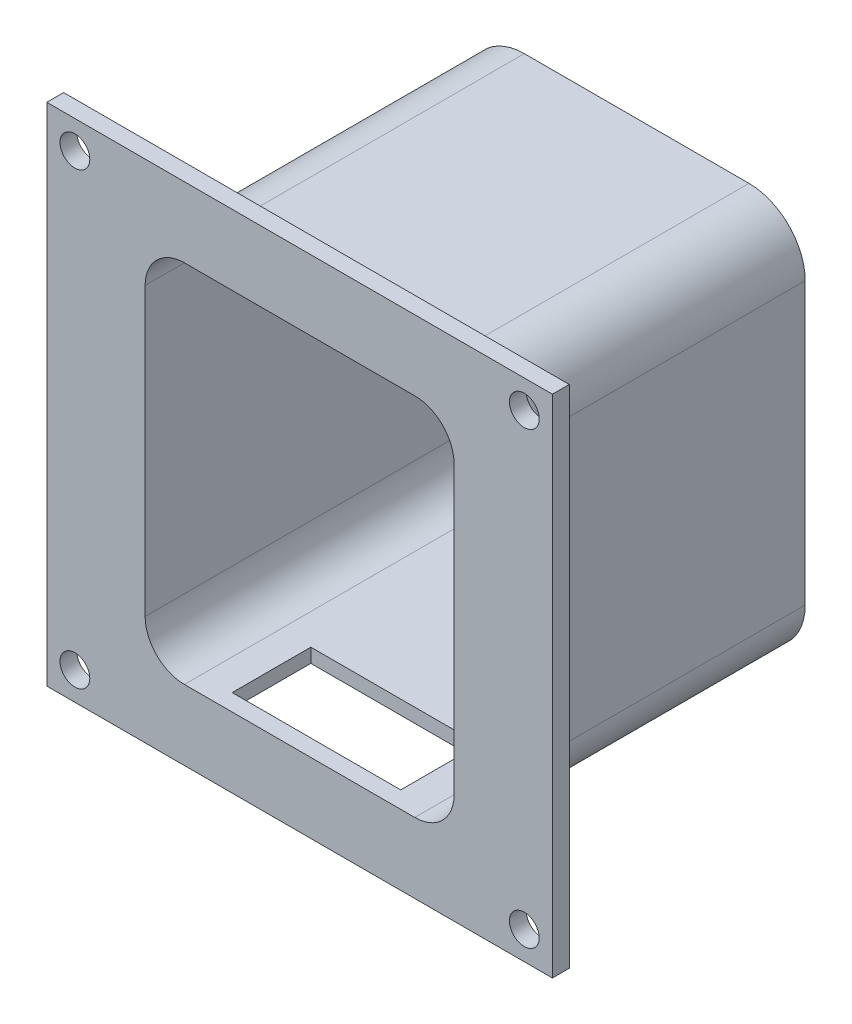
SolidWorks part; units mm, degrees
ref_plane "Front Plane" through (0, 0, 0) normal (0, 0, 1) x (1, 0, 0)
ref_plane "Top Plane" through (0, 0, 0) normal (0, 1, 0) x (1, 0, 0)
ref_plane "Right Plane" through (0, 0, 0) normal (1, 0, 0) x (0, 0, -1)
sketch "Sketch1" plane through (0, 0, 0) normal (0, 0, 1) x (1, 0, 0)
  line L1 (-30, -35) -> (30, -35)
  line L2 (-30, -35) -> (-30, 35)
  line L3 (-30, 35) -> (30, 35)
  line L4 (30, -35) -> (30, 35)
  line L5 (-30, -35) -> (30, 35) construction
  line L6 (-30, 35) -> (30, -35) construction
  line L7 (20.5, -32.5) -> (-20.5, -32.5)
  line L8 (27.5, -25.5) -> (27.5, 25.5)
  line L9 (20.5, 32.5) -> (-20.5, 32.5)
  line L10 (-27.5, -25.5) -> (-27.5, 25.5)
  line L11 (27.5, -32.5) -> (-27.5, 32.5) construction
  line L12 (27.5, 32.5) -> (-27.5, -32.5) construction
  arc A0 (-20.5, -32.5) -> (-27.5, -25.5) centre (-20.5, -25.5) cw
  arc A1 (20.5, -32.5) -> (27.5, -25.5) centre (20.5, -25.5) ccw
  arc A2 (27.5, 25.5) -> (20.5, 32.5) centre (20.5, 25.5) ccw
  arc A3 (-20.5, 32.5) -> (-27.5, 25.5) centre (-20.5, 25.5) ccw
  point P0 (0, 0)
  point P6 (0, 0)
  dimension "D3" = 7
  dimension "D1" = 70
  dimension "D2" = 60
  dimension "D4" = 65
  dimension "D5" = 55
extrude "Boss-Extrude1" add sketch "Sketch1" along normal blind 60
sketch "Sketch2" plane through (0, 0, 0) normal (0, 0, -1) x (-1, 0, 0)
  line L0 (0, 0.5) -> (0, -32.5) construction
  line L1 (-17.65, -4.5) -> (-10.65, -4.5)
  line L2 (-10.65, -4.5) -> (-10.65, -29.5)
  line L3 (-10.65, -29.5) -> (10.65, -29.5)
  line L4 (10.65, -29.5) -> (10.65, -4.5)
  line L5 (10.65, -4.5) -> (17.65, -4.5)
  line L6 (17.65, -4.5) -> (17.65, -25.5)
  line L7 (-17.65, -4.5) -> (-17.65, -25.5)
  line L8 (0, 0.5) -> (13.5, 0.5) construction
  line L9 (13.5, 0.5) -> (13.5, -8.5) construction
  line L10 (13.5, -8.5) -> (13.5, -16.5) construction
  line L11 (13.5, -16.5) -> (13.5, -24.5) construction
  line L12 (-20.5, -32.5) -> (20.5, -32.5)
  line L13 (-17.65, -25.5) -> (-27.5, -25.5)
  line L14 (17.65, -25.5) -> (27.5, -25.5)
  line L15 (20.5, -32.5) -> (-20.5, -32.5) construction
  circle A0 centre (0, 0.5) radius 11 construction
  circle A1 centre (13.5, -8.5) radius 1.25
  arc A2 (-27.5, -25.5) -> (-20.5, -32.5) centre (-20.5, -25.5) ccw
  circle A3 centre (13.5, -16.5) radius 1.25
  circle A4 centre (13.5, -24.5) radius 1.25
  circle A5 centre (-13.5, -8.5) radius 1.25
  circle A6 centre (-13.5, -16.5) radius 1.25
  circle A7 centre (-13.5, -24.5) radius 1.25
  arc A8 (20.5, -32.5) -> (27.5, -25.5) centre (20.5, -25.5) ccw
  arc A9 (-27.5, -25.5) -> (-20.5, -32.5) centre (-20.5, -25.5) ccw construction
  point P6 (0, -29.5)
  point P31 (0, 0)
  point P34 (0, -32.5)
  dimension "D1" = 22
  dimension "D5" = 2.5
  dimension "D2" = 21.3
  dimension "D3" = 13.5
  dimension "D4" = 9
  dimension "D6" = 8
  dimension "D7" = 8
  dimension "D8" = 7
  dimension "D9" = 5
  dimension "D10" = 3
  dimension "D11" = 30
extrude "Boss-Extrude2" add sketch "Sketch2" against normal blind 3.5
sketch "Sketch4" plane through (0, -35, 0) normal (0, -1, 0) x (1, 0, 0)
  line L0 (-30, 60) -> (30, 60) construction
  line L1 (15, 60) -> (-15, 60)
  line L2 (15, 60) -> (15, 43)
  line L3 (15, 43) -> (-15, 43)
  line L4 (-15, 60) -> (-15, 43)
  line L5 (0, 0) -> (0, 60) construction
  line L6 (-30, 0) -> (30, 0) construction
  point P10 (0, 60)
  dimension "D1" = 30
  dimension "D2" = 17
extrude "Cut-Extrude1" cut sketch "Sketch4" against normal up to surface (2.5 mm away) up to face at (0, -32.5, 31.75)
sketch "Sketch5" plane through (0, 0, 0) normal (0, 0, -1) x (-1, 0, 0)
  circle A0 centre (-13.5, -8.5) radius 2.25
  circle A1 centre (-13.5, -16.5) radius 2.25
  circle A2 centre (-13.5, -24.5) radius 2.25
  circle A3 centre (13.5, -24.5) radius 2.25
  circle A4 centre (13.5, -16.5) radius 2.25
  circle A5 centre (13.5, -8.5) radius 2.25
  dimension "D1" = 4.5
extrude "Cut-Extrude2" cut sketch "Sketch5" against normal blind 3
sketch "Sketch6" plane through (0, 0, 60) normal (0, 0, 1) x (1, 0, 0)
  line L1 (-45, 45) -> (45, 45)
  line L2 (-45, 45) -> (-45, -45)
  line L3 (-45, -45) -> (45, -45)
  line L4 (45, 45) -> (45, -45)
  line L5 (-45, 45) -> (45, -45) construction
  line L6 (-45, -45) -> (45, 45) construction
  line L7 (40, 40) -> (-40, 40) construction
  line L8 (40, 40) -> (40, -40) construction
  line L9 (40, -40) -> (-40, -40) construction
  line L10 (-40, 40) -> (-40, -40) construction
  line L11 (40, 40) -> (-40, -40) construction
  line L12 (40, -40) -> (-40, 40) construction
  circle A0 centre (40, 40) radius 2.65
  circle A1 centre (-40, 40) radius 2.65
  circle A2 centre (-40, -40) radius 2.65
  circle A3 centre (40, -40) radius 2.65
  point P0 (0, 0)
  point P6 (0, 0)
  dimension "D5" = 5.3
  dimension "D1" = 90
  dimension "D2" = 90
  dimension "D3" = 80
  dimension "D4" = 80
extrude "Boss-Extrude3" add sketch "Sketch6" against normal blind 3
fillet "Fillet1" radius 10 4 edges at (-30, -35, 28.5) (30, -35, 28.5) (-30, 35, 28.5) (30, 35, 28.5)
sketch "Sketch8" plane through (0, 0, 57) normal (0, 0, -1) x (-1, 0, 0)
  line L0 (-20.5, 32.5) -> (20.5, 32.5) construction
  line L1 (-20.5, 32.5) -> (20.5, 32.5)
  line L2 (27.5, 25.5) -> (27.5, -25.5) construction
  line L3 (27.5, 25.5) -> (27.5, -25.5)
  line L4 (-27.5, -25.5) -> (-27.5, 25.5) construction
  line L5 (-27.5, -25.5) -> (-27.5, 25.5)
  line L6 (-20.5, -32.5) -> (20.5, -32.5)
  arc A0 (-20.5, 32.5) -> (-27.5, 25.5) centre (-20.5, 25.5) ccw construction
  arc A1 (-20.5, 32.5) -> (-27.5, 25.5) centre (-20.5, 25.5) ccw
  arc A2 (27.5, 25.5) -> (20.5, 32.5) centre (20.5, 25.5) ccw construction
  arc A3 (27.5, 25.5) -> (20.5, 32.5) centre (20.5, 25.5) ccw
  arc A4 (20.5, -32.5) -> (27.5, -25.5) centre (20.5, -25.5) ccw construction
  arc A5 (20.5, -32.5) -> (27.5, -25.5) centre (20.5, -25.5) ccw
  arc A6 (-27.5, -25.5) -> (-20.5, -32.5) centre (-20.5, -25.5) ccw construction
  arc A7 (-27.5, -25.5) -> (-20.5, -32.5) centre (-20.5, -25.5) ccw
extrude "Cut-Extrude5" cut sketch "Sketch8" against normal through all
fillet "Fillet3" radius 5 2 edges at (-17.65, -25.5, 1.75) (17.65, -25.5, 1.75)
fillet "Fillet4" radius 5 2 edges at (-27.5, -25.5, 1.75) (27.5, -25.5, 1.75)
